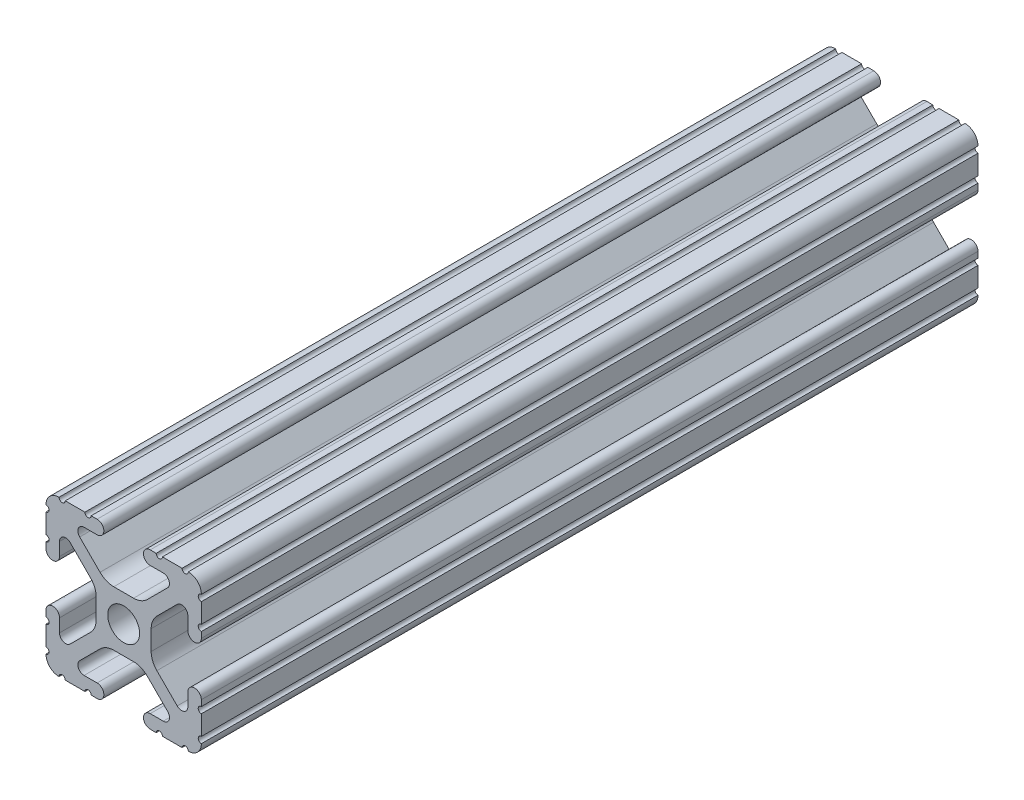
SolidWorks part; units mm, degrees
ref_plane "Front Plane" through (0, 0, 0) normal (0, 0, 1) x (1, 0, 0)
ref_plane "Top Plane" through (0, 0, 0) normal (0, 1, 0) x (1, 0, 0)
ref_plane "Right Plane" through (0, 0, 0) normal (1, 0, 0) x (0, 0, -1)
sketch "Sketch1" plane through (0, 0, 0) normal (0, 0, 1) x (1, 0, 0)
  line L0 (-12.7, -6.3331) -> (-12.7, -9.5504)
  line L1 (-9.5504, -12.7) -> (-6.3331, -12.7)
  line L2 (-5.3171, -12.7) -> (-4.3434, -12.7)
  line L3 (-4.3434, -10.4902) -> (-6.4748, -10.4902)
  line L4 (-7.1932, -8.7558) -> (-3.8632, -5.4257)
  line L5 (-1.6181, -4.4958) -> (1.6181, -4.4958)
  line L6 (3.8632, -5.4257) -> (7.1932, -8.7558)
  line L7 (6.4748, -10.4902) -> (4.3434, -10.4902)
  line L8 (4.3434, -12.7) -> (5.3171, -12.7)
  line L9 (6.3331, -12.7) -> (9.5504, -12.7)
  line L10 (12.7, -9.5504) -> (12.7, -6.3331)
  line L11 (12.7, -5.3171) -> (12.7, -4.3434)
  line L12 (10.4902, -4.3434) -> (10.4902, -6.4748)
  line L13 (8.7558, -7.1932) -> (5.4257, -3.8632)
  line L14 (4.4958, -1.6181) -> (4.4958, 1.6181)
  line L15 (5.4257, 3.8632) -> (8.7558, 7.1932)
  line L16 (10.4902, 6.4748) -> (10.4902, 4.3434)
  line L17 (12.7, 4.3434) -> (12.7, 5.3171)
  line L18 (12.7, 6.3331) -> (12.7, 9.5504)
  line L19 (9.5504, 12.7) -> (6.3331, 12.7)
  line L20 (5.3171, 12.7) -> (4.3434, 12.7)
  line L21 (4.3434, 10.4902) -> (6.4748, 10.4902)
  line L22 (7.1932, 8.7558) -> (3.8632, 5.4257)
  line L23 (1.6181, 4.4958) -> (-1.6181, 4.4958)
  line L24 (-3.8632, 5.4257) -> (-7.1932, 8.7558)
  line L25 (-6.4748, 10.4902) -> (-4.3434, 10.4902)
  line L26 (-4.3434, 12.7) -> (-5.3171, 12.7)
  line L27 (-6.3331, 12.7) -> (-9.5504, 12.7)
  line L28 (-12.7, 9.5504) -> (-12.7, 6.3331)
  line L29 (-12.7, 5.3171) -> (-12.7, 4.3434)
  line L30 (-10.4902, 4.3434) -> (-10.4902, 6.4748)
  line L31 (-8.7558, 7.1932) -> (-5.4257, 3.8632)
  line L32 (-4.4958, 1.6181) -> (-4.4958, -1.6181)
  line L33 (-5.4257, -3.8632) -> (-8.7558, -7.1932)
  line L34 (-10.4902, -6.4748) -> (-10.4902, -4.3434)
  line L35 (-12.7, -4.3434) -> (-12.7, -5.3171)
  circle A0 centre (0, 0) radius 2.6035
  arc A1 (-12.7, -5.3171) -> (-12.7, -6.3331) centre (-12.7, -5.8251) cw
  arc A2 (-12.7, -9.5504) -> (-12.6998, -10.5664) centre (-12.7, -10.0584) cw
  arc A3 (-12.6998, -10.5664) -> (-10.5664, -12.6998) centre (-10.5918, -10.5918) ccw
  arc A4 (-10.5664, -12.6998) -> (-9.5504, -12.7) centre (-10.0584, -12.7) cw
  arc A5 (-6.3331, -12.7) -> (-5.3171, -12.7) centre (-5.8251, -12.7) cw
  arc A6 (-4.3434, -12.7) -> (-4.3434, -10.4902) centre (-4.3434, -11.5951) ccw
  arc A7 (-6.4748, -10.4902) -> (-7.1932, -8.7558) centre (-6.4748, -9.4742) cw
  arc A8 (-3.8632, -5.4257) -> (-1.6181, -4.4958) centre (-1.6181, -7.6708) cw
  arc A9 (1.6181, -4.4958) -> (3.8632, -5.4257) centre (1.6181, -7.6708) cw
  arc A10 (7.1932, -8.7558) -> (6.4748, -10.4902) centre (6.4748, -9.4742) cw
  arc A11 (4.3434, -10.4902) -> (4.3434, -12.7) centre (4.3434, -11.5951) ccw
  arc A12 (5.3171, -12.7) -> (6.3331, -12.7) centre (5.8251, -12.7) cw
  arc A13 (9.5504, -12.7) -> (10.5664, -12.6998) centre (10.0584, -12.7) cw
  arc A14 (10.5664, -12.6998) -> (12.6998, -10.5664) centre (10.5918, -10.5918) ccw
  arc A15 (12.6998, -10.5664) -> (12.7, -9.5504) centre (12.7, -10.0584) cw
  arc A16 (12.7, -6.3331) -> (12.7, -5.3171) centre (12.7, -5.8251) cw
  arc A17 (12.7, -4.3434) -> (10.4902, -4.3434) centre (11.5951, -4.3434) ccw
  arc A18 (10.4902, -6.4748) -> (8.7558, -7.1932) centre (9.4742, -6.4748) cw
  arc A19 (5.4257, -3.8632) -> (4.4958, -1.6181) centre (7.6708, -1.6181) cw
  arc A20 (4.4958, 1.6181) -> (5.4257, 3.8632) centre (7.6708, 1.6181) cw
  arc A21 (8.7558, 7.1932) -> (10.4902, 6.4748) centre (9.4742, 6.4748) cw
  arc A22 (10.4902, 4.3434) -> (12.7, 4.3434) centre (11.5951, 4.3434) ccw
  arc A23 (12.7, 5.3171) -> (12.7, 6.3331) centre (12.7, 5.8251) cw
  arc A24 (12.7, 9.5504) -> (12.6998, 10.5664) centre (12.7, 10.0584) cw
  arc A25 (12.6998, 10.5664) -> (10.5664, 12.6998) centre (10.5918, 10.5918) ccw
  arc A26 (10.5664, 12.6998) -> (9.5504, 12.7) centre (10.0584, 12.7) cw
  arc A27 (6.3331, 12.7) -> (5.3171, 12.7) centre (5.8251, 12.7) cw
  arc A28 (4.3434, 12.7) -> (4.3434, 10.4902) centre (4.3434, 11.5951) ccw
  arc A29 (6.4748, 10.4902) -> (7.1932, 8.7558) centre (6.4748, 9.4742) cw
  arc A30 (3.8632, 5.4257) -> (1.6181, 4.4958) centre (1.6181, 7.6708) cw
  arc A31 (-1.6181, 4.4958) -> (-3.8632, 5.4257) centre (-1.6181, 7.6708) cw
  arc A32 (-7.1932, 8.7558) -> (-6.4748, 10.4902) centre (-6.4748, 9.4742) cw
  arc A33 (-4.3434, 10.4902) -> (-4.3434, 12.7) centre (-4.3434, 11.5951) ccw
  arc A34 (-5.3171, 12.7) -> (-6.3331, 12.7) centre (-5.8251, 12.7) cw
  arc A35 (-9.5504, 12.7) -> (-10.5664, 12.6998) centre (-10.0584, 12.7) cw
  arc A36 (-10.5664, 12.6998) -> (-12.6998, 10.5664) centre (-10.5918, 10.5918) ccw
  arc A37 (-12.6998, 10.5664) -> (-12.7, 9.5504) centre (-12.7, 10.0584) cw
  arc A38 (-12.7, 6.3331) -> (-12.7, 5.3171) centre (-12.7, 5.8251) cw
  arc A39 (-12.7, 4.3434) -> (-10.4902, 4.3434) centre (-11.5951, 4.3434) ccw
  arc A40 (-10.4902, 6.4748) -> (-8.7558, 7.1932) centre (-9.4742, 6.4748) cw
  arc A41 (-5.4257, 3.8632) -> (-4.4958, 1.6181) centre (-7.6708, 1.6181) cw
  arc A42 (-4.4958, -1.6181) -> (-5.4257, -3.8632) centre (-7.6708, -1.6181) cw
  arc A43 (-8.7558, -7.1932) -> (-10.4902, -6.4748) centre (-9.4742, -6.4748) cw
  arc A44 (-10.4902, -4.3434) -> (-12.7, -4.3434) centre (-11.5951, -4.3434) ccw
extrude "Boss-Extrude1" add sketch "Sketch1" against normal blind 127
